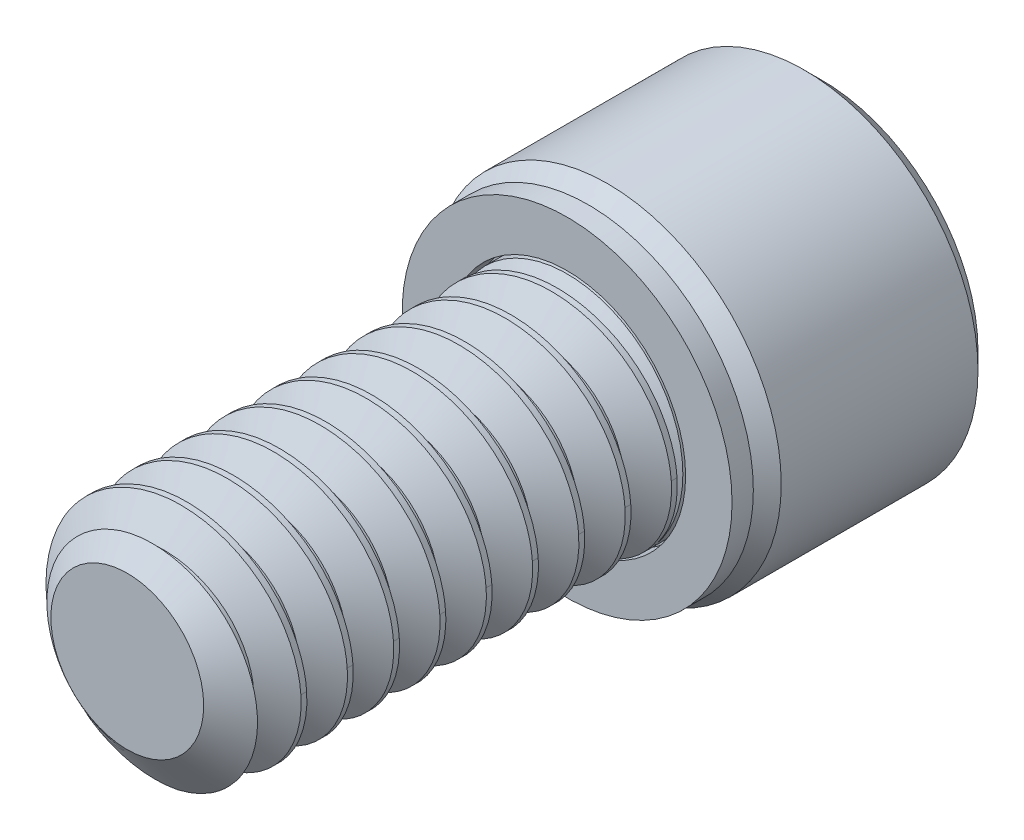
SolidWorks part; units mm, degrees
other "DetailItem1"
ref_plane "Front Plane" through (0, 0, 0) normal (0, 0, 1) x (1, 0, 0)
ref_plane "Top Plane" through (0, 0, 0) normal (0, 1, 0) x (1, 0, 0)
ref_plane "Right Plane" through (0, 0, 0) normal (1, 0, 0) x (0, 0, -1)
sketch "Sketch1" plane through (0, 0, 0) normal (0, 0, 1) x (1, 0, 0)
  circle A0 centre (0, 0) radius 3.175
  dimension "OD" = 6.35
extrude "Extrude1" add sketch "Sketch1" against normal blind 12.7
sketch "Sketch2" plane through (0, 0, 0) normal (0, 0, 1) x (1, 0, 0)
  circle A0 centre (0, 0) radius 3.175 construction
  circle A1 centre (0, 0) radius 3.175
curve "Helix/Spiral1" pitch 1.27 height 13.97 turns 11 parameters "pitch"=1.27
sketch "Sketch3" plane through (0, 0, 0) normal (1, 0, 0) x (0, 0, -1)
  line L0 (-1.1112, 3.175) -> (-0.635, 2.3501)
  line L1 (-0.635, 2.3501) -> (-0.4763, 2.3501)
  line L2 (-0.4763, 2.3501) -> (0, 3.175)
  line L3 (-1.1112, 3.175) -> (0, 3.175)
  line L4 (-0.5556, 3.175) -> (-0.5556, 2.3501) construction
  line L5 (-0.8731, 2.7626) -> (-0.2381, 2.7626) construction
  line L6 (0, 3.175) -> (0, -3.175) construction
  dimension "D1" = 0.1588
  dimension "D2" = 0.635
  dimension "D3" = 60
sweep "Cut-Sweep1" cut profiles "Sketch3" path "Helix/Spiral1"
sketch "Sketch4" plane through (0, 0, 0) normal (1, 0, 0) x (0, 0, -1)
  line L0 (0.7554, 3.175) -> (0, 2.0961)
  line L1 (0, 2.0961) -> (0, 3.175)
  line L2 (0.7554, 3.175) -> (0, 3.175)
  line L3 (-1.1112, 3.175) -> (0, 3.175) construction
  line L4 (0, 0) -> (7.0209, 0) construction
  dimension "D1" = 55
  dimension "D2" = 0.254
revolve "Cut-Revolve1" cut sketch "Sketch4" angle 360 about L4
sketch "Sketch6" plane through (0, 0, -12.7) normal (0, 0, -1) x (-1, 0, 0)
  circle A0 centre (0, 0) radius 4.7625
  dimension "head dia" = 9.525
extrude "Extrude2" add sketch "Sketch6" along normal blind 6.35
sketch "Sketch7" plane through (0, 0, -19.05) normal (0, 0, -1) x (-1, 0, 0)
  line L1 (0, 2.7496) -> (-2.3813, 1.3748)
  line L2 (-2.3813, 1.3748) -> (-2.3813, -1.3748)
  line L3 (-2.3813, -1.3748) -> (0, -2.7496)
  line L4 (0, -2.7496) -> (2.3813, -1.3748)
  line L5 (2.3813, -1.3748) -> (2.3813, 1.3748)
  line L6 (2.3813, 1.3748) -> (0, 2.7496)
  circle A0 centre (0, 0) radius 2.3813 construction
  dimension "hex dia" = 4.7625
extrude "Cut-Extrude1" cut sketch "Sketch7" against normal blind 3.5719
sketch "Sketch8" plane through (0, 0, -19.05) normal (0, 0, -1) x (-1, 0, 0)
  circle A0 centre (0, 0) radius 2.7496
extrude "Cut-Extrude2" cut sketch "Sketch8" against normal through all draft 45
chamfer "Chamfer1" distance 0.4763 angle 45 2 edges at (-4.7625, 0, -19.05) (-4.7625, 0, -12.7)
sketch "Sketch10" plane through (0, 0, -12.7) normal (0, 0, 1) x (1, 0, 0)
  circle A1 centre (0, 0) radius 3.175
  circle A2 centre (0, 0) radius 3.175
  dimension "D1" = 0
ref_plane "Plane1" through (0, 0, 0) normal (0, 0, 1) x (1, 0, 0)
extrude "partial thread" [suppressed] add sketch "Sketch10" along normal up to surface (12.7 mm away) separate body
chamfer "Chamfer2" [suppressed] distance 0.127 angle 45
combine bodies "Combine1" [suppressed] operation type add bodies to combine 107 108
sketch "Sketch9" plane through (0, 0, 0) normal (1, 0, 0) x (0, 0, -1)
  line L0 (0, 3.175) -> (0, -3.175) construction
  line L1 (3.175, 3.175) -> (3.175, -3.175) construction
  dimension "D1" = 3.175
sketch "Sketch11" plane through (0, 0, -12.7) normal (0, 0, 1) x (1, 0, 0)
  circle A1 centre (0, 0) radius 3.175
  circle A2 centre (0, 0) radius 3.175
  dimension "D1" = 0
extrude "Boss-Extrude1" add sketch "Sketch11" along normal blind 0.635 separate body
sketch "Sketch12" plane through (0, 0, -12.065) normal (0, 0, 1) x (1, 0, 0)
  circle A1 centre (0, 0) radius 3.175
  circle A2 centre (0, 0) radius 3.175
  dimension "D1" = 0
extrude "Boss-Extrude2" add sketch "Sketch12" along normal blind 2.54 draft 60
ref_plane "Plane2" through (0, 0, -12.6492) normal (0, 0, 1) x (1, 0, 0)
sketch "Sketch14" plane through (0, 0, -12.6492) normal (0, 0, 1) x (1, 0, 0)
  line L0 (0, 3.2512) -> (0, 4.2863) construction
  line L1 (0, 4.2863) -> (0, 4.7625) construction
  circle A1 centre (0, 0) radius 4.2862 construction
  circle A2 centre (0, 0) radius 3.2512
  circle A3 centre (0, 0) radius 3.2512
  circle A4 centre (0, 0) radius 4.7625 construction
  circle A5 centre (0, 0) radius 4.5244
  point P7 (0, 4.5244)
  dimension "D1" = 0.0762
extrude "Boss-Extrude3" add sketch "Sketch14" along normal up to vertex (0.5842 mm away) separate body
equation "\"D3@Helix/Spiral1\" = \"screw length@Extrude1\"+\"pitch@Helix/Spiral1\""
equation "\"D1@Sketch3\" = \"pitch@Helix/Spiral1\"*.125"
equation "\"D2@Sketch3\" = \"pitch@Helix/Spiral1\"*.5"
equation "\"D1@Cut-Extrude1\" = \"hex dia@Sketch7\"*.75"
equation "\"D1@Chamfer1\" = \"head dia@Sketch6\"*.05"
equation "\"D1@Sketch9\" = \"pitch@Helix/Spiral1\"*2.5"
equation "\"D1@Chamfer2\"=\"OD@Sketch1\"*.02"
equation "\"D1@Boss-Extrude1\" = \"pitch@helix/Spiral1\"*.5"
